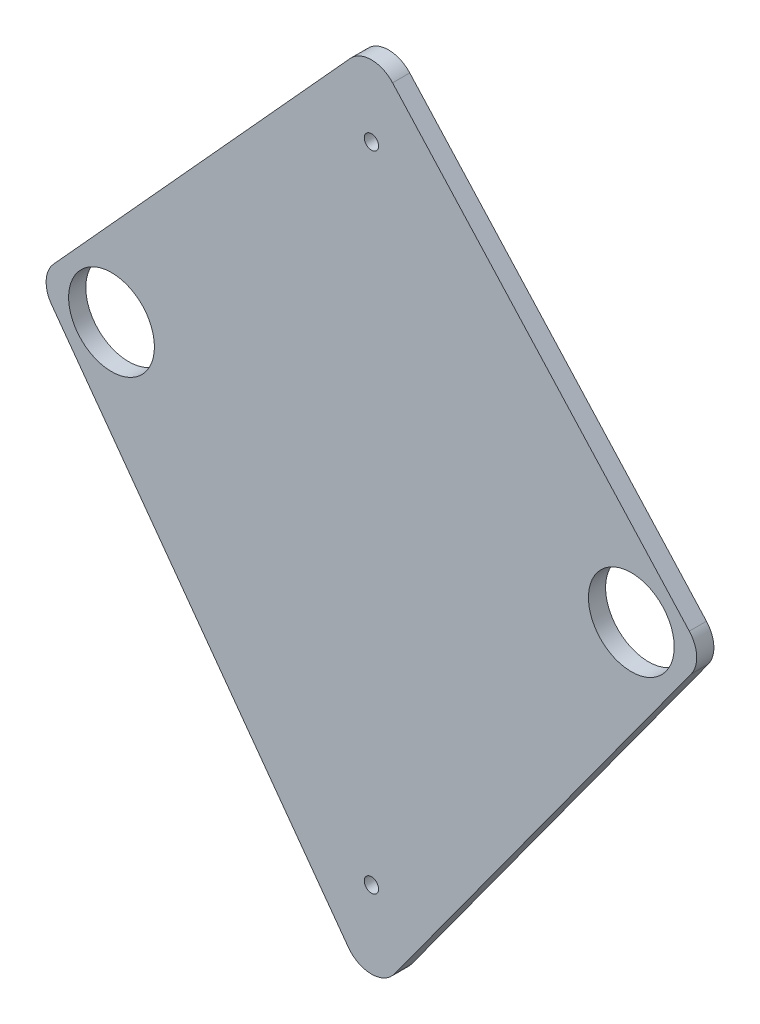
SolidWorks part; units mm, degrees
ref_plane "Front Plane" through (0, 0, 0) normal (0, 0, 1) x (1, 0, 0)
ref_plane "Top Plane" through (0, 0, 0) normal (0, 1, 0) x (1, 0, 0)
ref_plane "Right Plane" through (0, 0, 0) normal (1, 0, 0) x (0, 0, -1)
sketch "Sketch1" plane through (0, 0, 0) normal (0, 0, 1) x (1, 0, 0)
  line L0 (-90.88, 0) -> (90.88, 0) construction
  line L1 (0, -159.0108) -> (0, 129.7373) construction
  line L2 (0, 129.7373) -> (-116.6286, 1.4048)
  line L3 (-116.6286, 1.4048) -> (0, -159.0108)
  line L4 (116.6286, 1.4048) -> (0, -159.0108)
  line L5 (0, 129.7373) -> (116.6286, 1.4048)
  circle A0 centre (-90.88, 0) radius 15
  circle A1 centre (90.88, 0) radius 15
  circle A2 centre (0, -125) radius 2.5
  circle A3 centre (0, 100) radius 2.5
  circle A4 centre (0, -125) radius 12.7 construction
  circle A5 centre (0, 100) radius 12.7 construction
  dimension "D1" = 30
  dimension "D2" = 30
  dimension "D6" = 5
  dimension "D7" = 25.4
  dimension "D3" = 181.76
  dimension "D4" = 100
  dimension "D5" = 125
  dimension "D8" = 20
  dimension "D9" = 20
  dimension "D10" = 20
  dimension "D11" = 20
extrude "Boss-Extrude1" add sketch "Sketch1" along normal blind 6
fillet "Fillet1" radius 10 4 edges at (0, -159.0108, 3) (116.6286, 1.4048, 3) (0, 129.7373, 3) (-116.6286, 1.4048, 3)
equation "\"carbon_fiber_tube_diam\"= 1in"
equation "\"clip_tube_diam\"= 6mm"
equation "\"middle_tube_len\"= 500mm"
equation "\"horizontal_pipe_spacing\"= 250mm"
equation "\"D7@Sketch1\"=\"carbon_fiber_tube_diam\""
